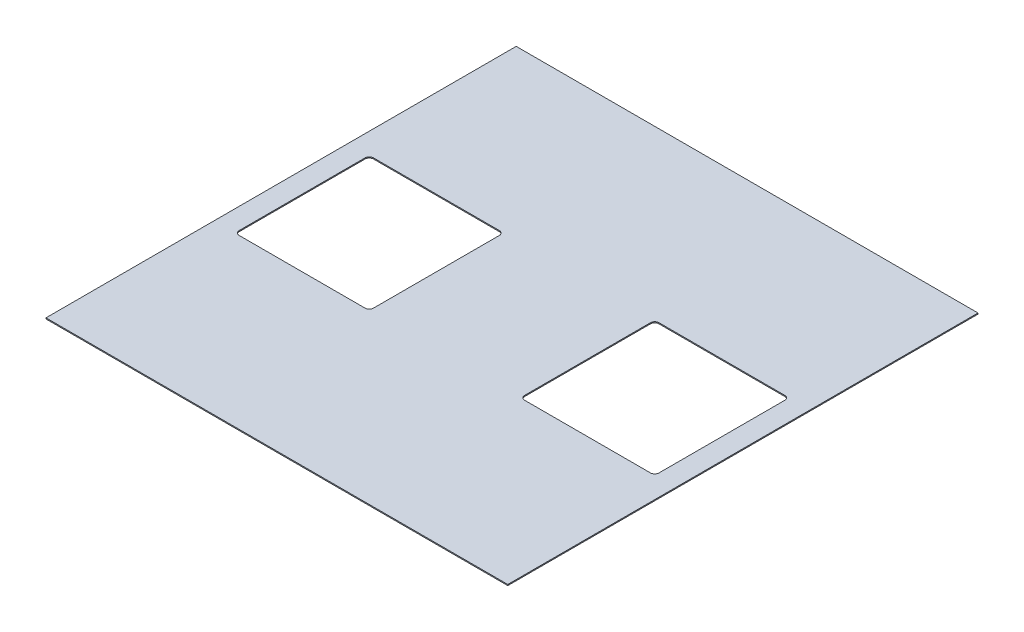
SolidWorks part; units mm, degrees
ref_plane "Front Plane" through (0, 0, 0) normal (0, 0, 1) x (1, 0, 0)
ref_plane "Top Plane" through (0, 0, 0) normal (0, 1, 0) x (1, 0, 0)
ref_plane "Right Plane" through (0, 0, 0) normal (1, 0, 0) x (0, 0, -1)
sketch "Sketch1" plane through (0, 0, 0) normal (0, 1, 0) x (1, 0, 0)
  line L6 (0, 0) -> (698.5, 0)
  line L11 (0, 0) -> (0, -711.2)
  line L12 (0, -711.2) -> (698.5, -711.2)
  line L17 (698.5, 0) -> (698.5, -711.2)
  line L18 (349.25, -711.2) -> (349.25, 0) construction
  line L22 (0, -355.6) -> (698.5, -355.6) construction
  line L24 (31.75, -254) -> (234.95, -254)
  line L25 (31.75, -254) -> (31.75, -457.2)
  line L26 (31.75, -457.2) -> (234.95, -457.2)
  line L27 (234.95, -254) -> (234.95, -457.2)
  line L28 (133.35, -457.2) -> (133.35, -254) construction
  line L29 (31.75, -355.6) -> (234.95, -355.6) construction
  line L30 (463.55, -254) -> (666.75, -254)
  line L31 (463.55, -254) -> (463.55, -457.2)
  line L32 (463.55, -457.2) -> (666.75, -457.2)
  line L33 (666.75, -254) -> (666.75, -457.2)
  line L34 (565.15, -457.2) -> (565.15, -254) construction
  line L35 (474.012, -355.6) -> (666.75, -355.6) construction
  point P60 (133.35, -355.6)
  point P77 (565.15, -355.6)
  point P133 (349.25, -355.6)
  dimension "D1" = 203.2
  dimension "D2" = 203.2
  dimension "D3" = 698.5
  dimension "D4" = 711.2
  dimension "D5" = 31.75
  dimension "D6" = 31.75
  dimension "D7" = 254
extrude "Boss-Extrude1" add sketch "Sketch1" along normal blind 1.5875
fillet "Fillet1" radius 6.35 8 edges at (666.75, 0.7937, 457.2) (666.75, 0.7937, 254) (463.55, 0.7937, 254) (463.55, 0.7937, 457.2) (234.95, 0.7937, 457.2) (31.75, 0.7937, 457.2) (234.95, 0.7937, 254) (31.75, 0.7937, 254)
